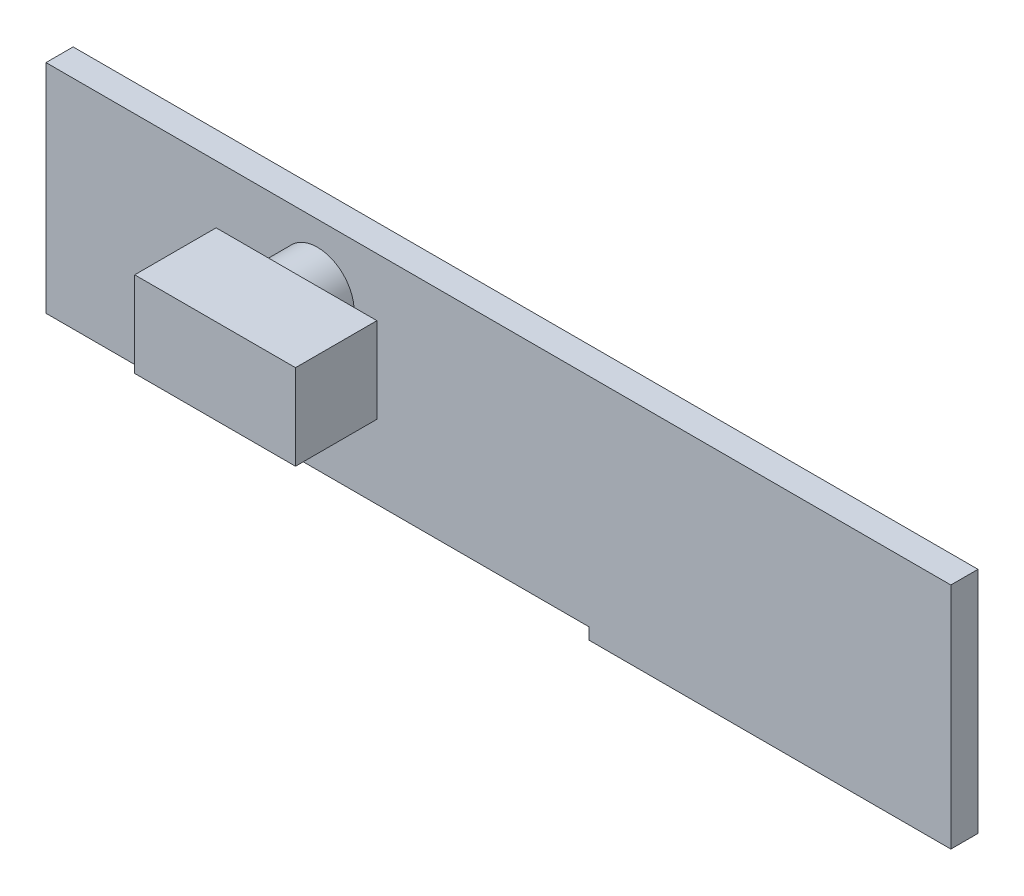
SolidWorks part; units mm, degrees
ref_plane "Front Plane" through (0, 0, 0) normal (0, 0, 1) x (1, 0, 0)
ref_plane "Top Plane" through (0, 0, 0) normal (0, 1, 0) x (1, 0, 0)
ref_plane "Right Plane" through (0, 0, 0) normal (1, 0, 0) x (0, 0, -1)
sketch "Sketch2" plane through (0, 0, 0) normal (0, 0, 1) x (1, 0, 0)
  line L1 (-47.8692, 21.2481) -> (206.1308, 21.2481)
  line L2 (-47.8692, 21.2481) -> (-47.8692, 8.5481)
  line L3 (-47.8692, 8.5481) -> (206.1308, 8.5481)
  line L4 (206.1308, 21.2481) -> (206.1308, 8.5481)
  dimension "D1" = 12.7
  dimension "D2" = 254
extrude "Boss-Extrude1" add sketch "Sketch2" along normal blind 101.6
sketch "Sketch3" plane through (0, 21.2481, 0) normal (0, 1, 0) x (1, 0, 0)
  circle A0 centre (79.1308, -28.4831) radius 17.1408
extrude "Boss-Extrude2" add sketch "Sketch3" along normal blind 19.05
sketch "Sketch4" plane through (0, 40.2981, 0) normal (0, 1, 0) x (1, 0, 0)
  line L1 (50.7675, -8.111) -> (126.0034, -8.111)
  line L2 (50.7675, -8.111) -> (50.7675, -48.0661)
  line L3 (50.7675, -48.0661) -> (126.0034, -48.0661)
  line L4 (126.0034, -8.111) -> (126.0034, -48.0661)
extrude "Boss-Extrude3" add sketch "Sketch4" along normal blind 38.1
scale "Scale2" scale about centroid uniform scaling yes scale factor 0.00375
move or copy body "rotate" bodies to move or copy 105 copy no rotation origin (0, 33.6669, 26.5501) rotation axis (1, 0, 0) rotation angle 90
move or copy body "-4 x" bodies to move or copy 106 copy no translate (-101.6, 0, 0)
move or copy body "-2 y" bodies to move or copy 117 copy no translate (0, -55.88, 0)
move or copy body "-2.1z" bodies to move or copy 121 copy no translate (0, 0, -30.48)
sketch "Sketch6" plane through (0, -39.7871, 0) normal (0, 1, 0) x (1, 0, 0)
  line L1 (-19.6967, 11.0887) -> (-19.0617, 11.0887)
  line L2 (-19.6967, 11.0887) -> (-19.6967, 11.0411)
  line L3 (-19.6967, 11.0411) -> (-19.0617, 11.0411)
  line L4 (-19.0617, 11.0887) -> (-19.0617, 11.0411)
  dimension "D1" = 0.635
extrude "Boss-Extrude6" add sketch "Sketch6" against normal blind 0.4013
